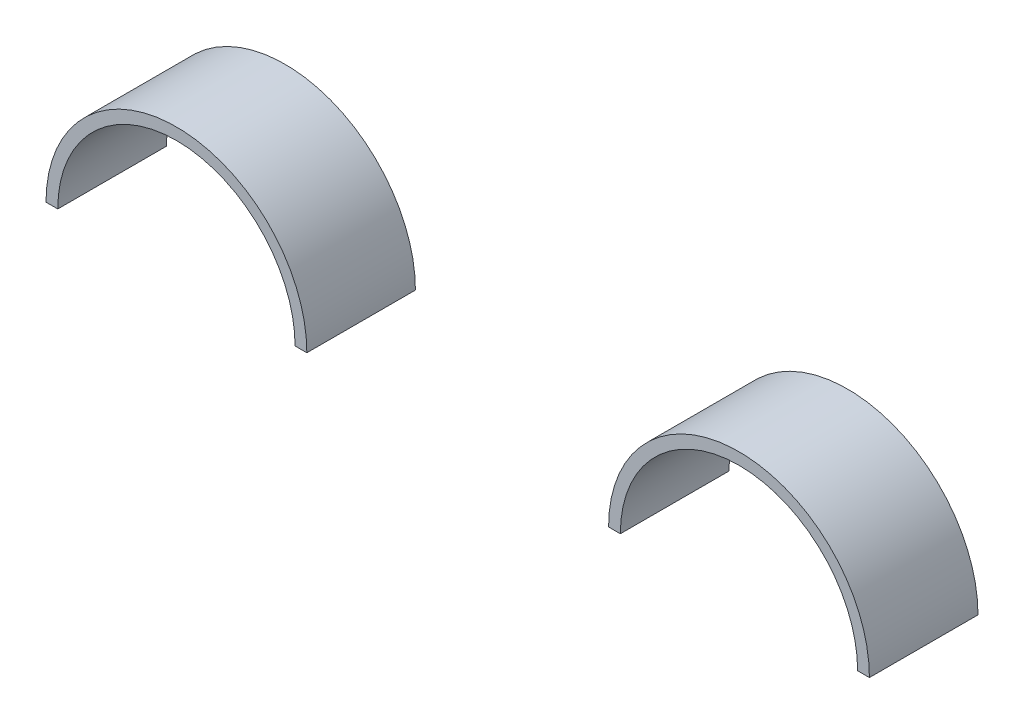
SolidWorks part; units mm, degrees
material "Velcro"
ref_plane "Front Plane" through (0, 0, 0) normal (0, 0, 1) x (1, 0, 0)
ref_plane "Top Plane" through (0, 0, 0) normal (0, 1, 0) x (1, 0, 0)
ref_plane "Right Plane" through (0, 0, 0) normal (1, 0, 0) x (0, 0, -1)
sketch "Sketch1" plane through (0, 0, 563.2423) normal (0, 0, -1) x (0, -1, 0)
  line L0 (326.7906, -1399.2805) -> (326.7906, -1487.9265) construction
  line L1 (326.7906, -1399.2805) -> (326.7906, -1487.9265) construction
  line L2 (326.7906, -1609.4345) -> (326.7906, -1698.0805) construction
  line L3 (326.7906, -1609.4345) -> (326.7906, -1698.0805) construction
  line L4 (326.7906, -1394.8805) -> (326.7906, -1399.2805)
  line L5 (326.7906, -1492.3265) -> (326.7906, -1487.9265)
  line L6 (326.7906, -1698.0805) -> (326.7906, -1702.4805)
  line L7 (326.7906, -1605.0345) -> (326.7906, -1609.4345)
  arc A0 (326.7906, -1698.0805) -> (326.7906, -1609.4345) centre (326.7906, -1653.7575) cw
  arc A1 (326.7906, -1487.9265) -> (326.7906, -1399.2805) centre (326.7906, -1443.6035) cw
  arc A2 (326.7906, -1492.3265) -> (326.7906, -1394.8805) centre (326.7906, -1443.6035) cw
  arc A3 (326.7906, -1702.4805) -> (326.7906, -1605.0345) centre (326.7906, -1653.7575) cw
  dimension "D1" = 4.4
  dimension "D2" = 4.4
extrude "Boss-Extrude1" add sketch "Sketch1" along normal blind 40.56
